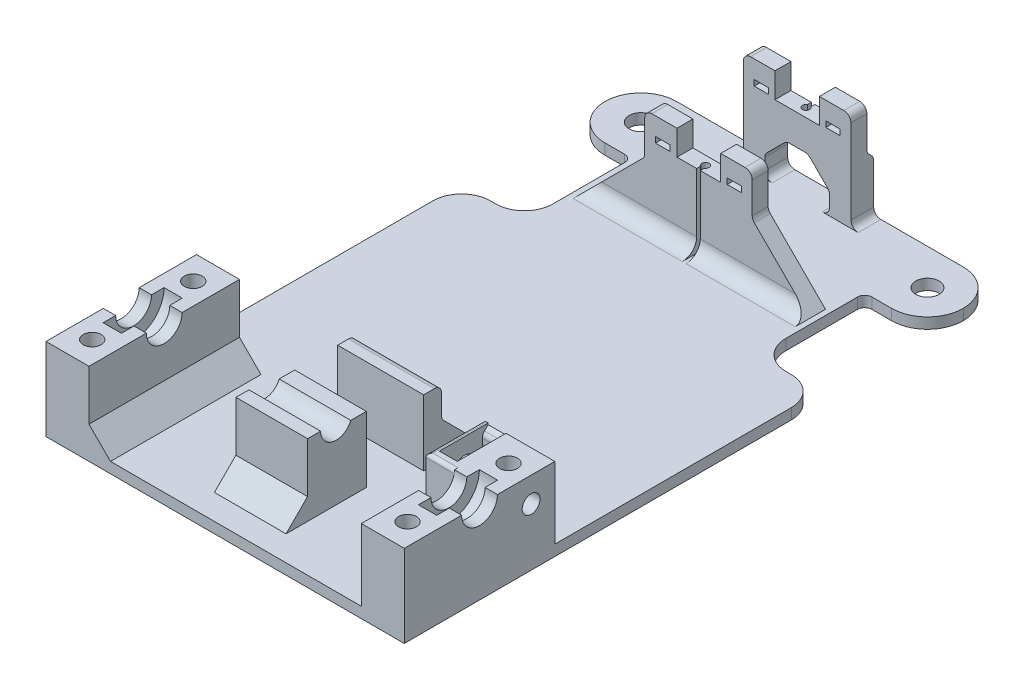
SolidWorks part; units mm, degrees
ref_plane "Front Plane" through (0, 0, 0) normal (0, 0, 1) x (1, 0, 0)
ref_plane "Top Plane" through (0, 0, 0) normal (0, 1, 0) x (1, 0, 0)
ref_plane "Right Plane" through (0, 0, 0) normal (1, 0, 0) x (0, 0, -1)
sketch "Sketch1" plane through (0, 0, 0) normal (0, 1, 0) x (1, 0, 0)
  line L0 (8, 116) -> (9.5, 116)
  line L1 (0, 0) -> (100, 0)
  line L2 (0, 0) -> (0, 108)
  line L5 (17.5, 124) -> (17.5, 146)
  line L7 (50, 0) -> (50, 146) construction
  line L8 (17.5, 146) -> (82.5, 146)
  line L9 (82.5, 124) -> (82.5, 146)
  line L10 (100, 0) -> (100, 108)
  line L11 (92, 116) -> (90.5, 116)
  arc A2 (9.5, 116) -> (17.5, 124) centre (9.5, 124) ccw
  arc A3 (8, 116) -> (0, 108) centre (8, 108) ccw
  arc A4 (92, 116) -> (100, 108) centre (92, 108) cw
  arc A5 (90.5, 116) -> (82.5, 124) centre (90.5, 124) cw
  dimension "D4" = 8
  dimension "D1" = 50
  dimension "D5" = 17.5
  dimension "D6" = 30
  dimension "D7" = 108
extrude "Boss-Extrude1" add sketch "Sketch1" along normal blind 3 contours L10 A4 L11 A5 L9 L8 L5 A2 L0 A3 L2 L1
ref_plane "Mid Plane" through (50, 0, 0) normal (-1, 0, 0) x (0, 0, 1)
sketch "Sketch2" plane through (0, 3, 0) normal (0, 1, 0) x (1, 0, 0)
  line L1 (0, 0) -> (12, 0)
  line L2 (0, 0) -> (0, 42)
  line L3 (0, 42) -> (12, 42)
  line L4 (12, 0) -> (12, 42)
  line L5 (100, 0) -> (88, 0)
  line L6 (100, 0) -> (100, 42)
  line L7 (100, 42) -> (88, 42)
  line L8 (88, 0) -> (88, 42)
  dimension "D1" = 42
  dimension "D2" = 12
extrude "Boss-Extrude2" add sketch "Sketch2" along normal blind 20
ref_plane "Plane1" through (6, 0, 0) normal (1, 0, 0) x (0, 0, -1)
sketch "Sketch3" plane through (6, 0, 0) normal (1, 0, 0) x (0, 0, -1)
  line L1 (0, 23) -> (42, 23) construction
  circle A0 centre (21, 23) radius 8.5
  point P6 (21, 23)
  dimension "D1" = 17
extrude "Cut-Extrude1" cut sketch "Sketch3" against normal mid plane 5.1
sketch "Sketch4" plane through (0, 0, 0) normal (-1, 0, 0) x (0, 0, 1)
  line L0 (-42, 23) -> (0, 23) construction
  circle A0 centre (-21, 23) radius 5
  dimension "D1" = 10
extrude "Cut-Extrude2" cut sketch "Sketch4" against normal up to surface (12 mm away) contours A0 up to face at (12, 13, -21)
mirror "Mirror7" about plane through (50, 0, 0) normal (-1, 0, 0) of "Cut-Extrude2", "Cut-Extrude1"
sketch "Sketch5" plane through (0, 3, 0) normal (0, 1, 0) x (1, 0, 0)
  line L0 (91.45, 21) -> (12, 21) construction
  line L1 (91.45, 12.5) -> (91.45, 29.5) construction
  line L2 (12, 16) -> (12, 26) construction
sketch "Sketch6" plane through (50, 0, 0) normal (1, 0, 0) x (0, 0, -1)
  line L0 (16.6344, 23) -> (13, 23)
  line L1 (29, 3) -> (13, 3)
  line L3 (26, 23) -> (25.3656, 23)
  line L4 (13, 3) -> (13, 23)
  line L5 (42, 3) -> (108, 3) construction
  line L6 (21, 3) -> (21, 18) construction
  line L7 (26, 23) -> (42, 23) construction
  line L8 (26, 23) -> (26, 3)
  line L9 (25.0619, 21.4) -> (26, 21.4)
  line L10 (26, 21.4) -> (29.4, 21.4)
  line L11 (29.4, 21.4) -> (29.4, 3)
  line L12 (29, 3) -> (29.4, 3)
  arc A0 (16, 23) -> (26, 23) centre (21, 23) ccw construction
  arc A2 (16.6344, 23) -> (25.3656, 23) centre (21, 23) ccw
  point P6 (21, 18.6344)
  dimension "D1" = 8.7312
  dimension "D2" = 16
  dimension "D3" = 1.6
  dimension "D4" = 3.4
extrude "Boss-Extrude3" add sketch "Sketch6" along normal mid plane 20 contours L0 A2 L3 L8 L1 L4 | L12 L1 L8 L10 L11 region at (50, 11.8875, -19.2724) region at (50, 12.2, -27.7)
chamfer "Chamfer1" distance 6 angle 45 2 edges at (12, 3, -21) (50, 3, -13)
chamfer "Chamfer2" [suppressed] distance 14 angle 45
sketch "Sketch7" plane through (0, 23, 0) normal (0, 1, 0) x (1, 0, 0)
  line L0 (6, 12.5) -> (6, 6.9) construction
  line L1 (8.55, 12.5) -> (3.45, 12.5) construction
  line L2 (6, 29.5) -> (6, 35.1) construction
  line L3 (3.45, 29.5) -> (8.55, 29.5) construction
  line L4 (50, 0) -> (50, 39.4651) construction
  line L5 (60, 0) -> (40, 0) construction
  line L6 (94, 29.5) -> (94, 35.1) construction
  line L7 (94, 12.5) -> (94, 6.9) construction
  circle A2 centre (6, 35.1) radius 2.5
  circle A3 centre (6, 6.9) radius 2.5
  circle A4 centre (94, 6.9) radius 2.5
  circle A5 centre (94, 35.1) radius 2.5
  dimension "D1" = 5
  dimension "D2" = 5.6
extrude "Cut-Extrude3" cut sketch "Sketch7" against normal up to next
sketch "Sketch8" plane through (0, 3, 0) normal (0, 1, 0) x (1, 0, 0)
  line L0 (36, 27) -> (36, 47) construction
  line L1 (18, 0) -> (88, 0) construction
  line L2 (30, 27) -> (30, 47) construction
  line L3 (0, 42) -> (0, 108) construction
  line L5 (30, 47) -> (36, 47) construction
  line L6 (36, 27) -> (30, 27) construction
  line L11 (29, 46.2) -> (37, 46.2)
  line L12 (29, 46.2) -> (29, 47.8)
  line L17 (29, 27.8) -> (37, 27.8)
  line L18 (29, 27.8) -> (29, 26.2)
  line L19 (29, 26.2) -> (37, 26.2)
  line L20 (37, 27.8) -> (37, 26.2)
  line L21 (29, 27.8) -> (37, 26.2) construction
  line L22 (29, 26.2) -> (37, 27.8) construction
  line L23 (29, 47.8) -> (37, 47.8)
  line L24 (37, 46.2) -> (37, 47.8)
  line L25 (29, 46.2) -> (37, 47.8) construction
  line L26 (29, 47.8) -> (37, 46.2) construction
  point P1 (33, 47)
  point P3 (33, 27)
  point P8 (33, 27)
  point P11 (33, 47)
  dimension "D5" = 6
  dimension "D2" = 20
  dimension "D3" = 27
  dimension "D4" = 36
  dimension "D7" = 8
  dimension "D8" = 1.6
extrude "Cut-Extrude4" cut sketch "Sketch8" against normal up to next
fillet "Fillet1" [suppressed] radius 2.54
sketch "Sketch9" plane through (0, 3, 0) normal (0, 1, 0) x (1, 0, 0)
  line L5 (80, 26) -> (88, 26)
  line L10 (49, 35.4) -> (80, 35.4) construction
  line L11 (49, 33.45) -> (49, 37.35) construction
  line L13 (80, 42) -> (88, 42)
  line L14 (80, 42) -> (80, 26)
  line L16 (88, 42) -> (88, 26)
  line L19 (88, 42) -> (88, 26) construction
  line L20 (100, 42) -> (88, 42) construction
  dimension "D2" = 8
extrude "Boss-Extrude4" add sketch "Sketch9" along normal up to surface (20 mm away) up to face at (94, 23, -37.6)
sketch "Sketch11" plane through (80, 0, 0) normal (-1, 0, 0) x (0, 0, 1)
  circle A0 centre (-35.4, 16) radius 5.55
  arc A2 (-36.4409, 14.92) -> (-36.3577, 17.1545) centre (-35.4, 16) ccw construction
  dimension "D3" = 11.1
extrude "Cut-Extrude6" cut sketch "Sketch11" against normal blind 5 from offset 1.4 offset against normal yes
sketch "Sketch12" plane through (80, 0, 0) normal (-1, 0, 0) x (0, 0, 1)
  line L0 (-40.4, 18.4088) -> (-40.4, 23)
  line L1 (-42, 23) -> (-26, 23) construction
  line L2 (-40.4, 23) -> (-30.4, 23)
  line L3 (-30.4, 23) -> (-30.4, 18.4088)
  line L4 (-35.4, 16) -> (-35.4, 23) construction
  circle A0 centre (-35.4, 16) radius 5.55 construction
  arc A1 (-30.4, 18.4088) -> (-40.4, 18.4088) centre (-35.4, 16) ccw
  dimension "D1" = 10
extrude "Cut-Extrude7" cut sketch "Sketch12" against normal blind 5 from offset 1.4 offset against normal yes
chamfer "Chamfer3" distance 2 angle 45 2 edges at (83.9, 23, -40.4) (83.9, 23, -30.4)
sketch "Sketch13" plane through (80, 0, 0) normal (-1, 0, 0) x (0, 0, 1)
  circle A0 centre (-35.4, 16) radius 2.5
  dimension "D1" = 5
extrude "Cut-Extrude8" cut sketch "Sketch13" against normal up to surface (20 mm away) up to face at (100, 11.625, -42.75)
fillet "Fillet3" radius 2 2 edges at (83.9, 21, -40.4) (83.9, 21, -30.4)
fillet "Fillet5" radius 1 2 edges at (84, 23, -26) (80, 23, -34) tangent propagation no
sketch "Sketch14" plane through (0, 3, 0) normal (0, 1, 0) x (1, 0, 0)
  line L1 (40, 41.4) -> (64, 41.4)
  line L2 (40, 41.4) -> (40, 46.4)
  line L3 (40, 46.4) -> (64, 46.4)
  line L4 (64, 41.4) -> (64, 46.4)
  line L5 (40, 25.0619) -> (40, 29.4) construction
  line L6 (60, 29.4) -> (40, 29.4) construction
  dimension "D1" = 24
  dimension "D2" = 5
  dimension "D3" = 12
extrude "Boss-Extrude5" add sketch "Sketch14" along normal up to surface (18.4 mm away) up to face at (50, 21.4, -27.2309)
chamfer "Chamfer4" distance 10 angle 45 1 edges at (52, 3, -46.4)
sketch "Sketch15" plane through (0, 3, 0) normal (0, 1, 0) x (1, 0, 0)
  line L0 (17.5, 146) -> (82.5, 146) construction
  line L1 (0, 146) -> (100, 146)
  line L2 (0, 146) -> (0, 166)
  line L3 (0, 166) -> (100, 166)
  line L4 (100, 146) -> (100, 166)
  line L5 (100, 42) -> (100, 108) construction
  line L6 (0, 156) -> (100, 156) construction
  line L7 (50, 166) -> (50, 156) construction
  circle A0 centre (90, 156) radius 3.25
  circle A1 centre (10, 156) radius 3.25
  point P6 (50, 146)
  point P7 (50, 146)
  point P19 (50, 161)
  dimension "D2" = 6.5
  dimension "D3" = 40
  dimension "D1" = 20
extrude "Boss-Extrude6" add sketch "Sketch15" against normal up to surface (3 mm away) up to face at (33, 0, -47)
sketch "Sketch16" plane through (0, 3, 0) normal (0, 1, 0) x (1, 0, 0)
  line L0 (100, 166) -> (0, 166) construction
  line L1 (35, 164.1) -> (49.5, 164.1)
  line L2 (35, 164.1) -> (35, 159.65)
  line L3 (35, 159.65) -> (65, 159.65)
  line L4 (65, 164.1) -> (65, 159.65)
  line L5 (49.5, 164.1) -> (49.5, 162.966)
  line L6 (50.5, 164.1) -> (50.5, 162.966)
  line L8 (50.5, 164.1) -> (65, 164.1)
  line L16 (49.5, 132.1) -> (49.5, 133.234)
  line L17 (35, 136.55) -> (65, 136.55)
  line L18 (35, 136.55) -> (35, 132.1)
  line L19 (35, 132.1) -> (49.5, 132.1)
  line L20 (65, 136.55) -> (65, 132.1)
  line L21 (50.5, 132.1) -> (50.5, 133.234)
  line L22 (50.5, 132.1) -> (65, 132.1)
  arc A0 (49.5, 162.966) -> (50.5, 162.966) centre (50, 162.1) ccw
  arc A2 (49.5, 133.234) -> (50.5, 133.234) centre (50, 134.1) cw
  point P6 (50, 166)
  point P7 (50, 136.55)
  point P13 (50, 159.65)
  dimension "D3" = 2
  dimension "D4" = 2
  dimension "D7" = 1
  dimension "D8" = 1
  dimension "D1" = 30
  dimension "D2" = 4.45
  dimension "D5" = 1
  dimension "D6" = 29.45
  dimension "D9" = 2
  dimension "D10" = 30
  dimension "D11" = 1.9
extrude "Boss-Extrude7" add sketch "Sketch16" along normal blind 20.5 contours L4 L3 L2 L1 L5 A0 L6 L8 | L18 L19 L16 A2 L21 L22 L20 L17
sketch "Sketch17" plane through (0, 0, -166) normal (0, 0, -1) x (-1, 0, 0)
  line L0 (-91.45, 3) -> (-12, 3) construction
  line L1 (-59, 3) -> (-41, 3)
  line L2 (-59, 3) -> (-59, 15)
  line L3 (-59, 15) -> (-41, 15)
  line L4 (-41, 3) -> (-41, 15)
  line L6 (-100, 0) -> (0, 0) construction
  point P13 (-50, 0)
  point P14 (-50, 3)
  dimension "D1" = 12
  dimension "D2" = 18
extrude "Cut-Extrude9" cut sketch "Sketch17" against normal up to surface (6.35 mm away) up to face at (50, 13.25, -159.65)
fillet "Fillet7" radius 10 4 edges at (0, 1.5, -146) (0, 1.5, -166) (100, 1.5, -166) (100, 1.5, -146)
chamfer "Chamfer5" distance 16 angle 45 4 edges at (35, 3, -134.325) (62, 3, -164.1) (38, 3, -164.1) (65, 3, -134.325)
chamfer "Chamfer6" distance 6 angle 45 2 edges at (41, 15, -162.825) (59, 15, -162.825)
fillet "Fillet6" radius 2 18 edges at (52, 13, -46.4) (52, 21.4, -46.4) (17.5, 1.5, -146) (82.5, 1.5, -146) (42.25, 19, -164.1) (57.75, 19, -164.1) (57.75, 17.1, -166) (42.25, 17.1, -166) (41, 9, -162.825) (47, 15, -162.825) (53, 15, -162.825) (59, 9, -162.825) (35, 3, -162.825) (65, 3, -162.825) (59, 3, -162.825) (41, 3, -162.825) (35, 19, -134.325) (65, 19, -134.325)
sketch "Sketch18" plane through (0, 23.5, 0) normal (0, 1, 0) x (1, 0, 0)
  line L1 (44.1, 136.55) -> (56.1, 136.55) construction
  line L2 (44.1, 136.55) -> (44.1, 132.1) construction
  line L3 (44.1, 132.1) -> (56.1, 132.1) construction
  line L4 (56.1, 136.55) -> (56.1, 132.1) construction
  line L5 (44.1, 136.55) -> (56.1, 132.1) construction
  line L6 (44.1, 132.1) -> (56.1, 136.55) construction
  line L7 (19, 132.1) -> (49.5, 132.1) construction
  line L8 (56.2, 132.1) -> (65, 132.1)
  line L9 (56.2, 132.1) -> (56.2, 136.55)
  line L10 (56.2, 136.55) -> (65, 136.55)
  line L11 (65, 132.1) -> (65, 136.55)
  line L12 (44, 132.1) -> (35, 132.1)
  line L13 (44, 132.1) -> (44, 136.55)
  line L14 (44, 136.55) -> (35, 136.55)
  line L15 (35, 132.1) -> (35, 136.55)
  line L16 (35, 136.55) -> (35, 132.1) construction
  line L17 (35, 136.55) -> (35, 132.1) construction
  line L18 (56.1, 134.325) -> (56.2, 134.325) construction
  line L19 (44, 134.325) -> (44.1, 134.325) construction
  line L20 (57, 159.65) -> (67, 159.65) construction
  line L21 (65, 159.65) -> (56.2, 159.65)
  line L22 (65, 159.65) -> (65, 164.1)
  line L23 (65, 164.1) -> (56.2, 164.1)
  line L24 (56.2, 159.65) -> (56.2, 164.1)
  line L25 (65, 164.1) -> (65, 159.65) construction
  line L27 (35, 164.1) -> (49.5, 164.1) construction
  line L28 (35, 159.65) -> (43.8, 159.65)
  line L29 (35, 159.65) -> (35, 164.1)
  line L30 (35, 164.1) -> (43.8, 164.1)
  line L31 (43.8, 159.65) -> (43.8, 164.1)
  line L32 (19, 136.55) -> (81, 136.55) construction
  point P0 (50.1, 134.325)
  dimension "D1" = 12
  dimension "D2" = 0.1
  dimension "D3" = 8.8
extrude "Boss-Extrude8" add sketch "Sketch18" along normal blind 7
fillet "Fillet9" radius 4 2 edges at (34.25, 3, -132.1) (65.75, 3, -132.1)
fillet "Fillet8" radius 2 4 edges at (35, 30.5, -134.325) (65, 30.5, -134.325) (35, 30.5, -161.875) (65, 30.5, -161.875)
sketch "Sketch19" plane through (0, 0, -164.1) normal (0, 0, -1) x (-1, 0, 0)
  line L0 (-40, 30.5) -> (-40, 25.5) construction
  line L3 (-62, 23.9) -> (-58, 23.9)
  line L4 (-62, 23.9) -> (-62, 25.5)
  line L5 (-62, 25.5) -> (-58, 25.5)
  line L6 (-58, 23.9) -> (-58, 25.5)
  line L9 (-42, 23.9) -> (-38, 23.9)
  line L10 (-42, 23.9) -> (-42, 25.5)
  line L11 (-42, 25.5) -> (-38, 25.5)
  line L12 (-38, 23.9) -> (-38, 25.5)
  line L14 (-60, 30.5) -> (-60, 25.5) construction
  line L16 (-35, 28.5) -> (-35, 19.8284) construction
  line L17 (-65, 28.5) -> (-65, 19.8284) construction
  line L18 (-43.8, 30.5) -> (-37, 30.5) construction
  dimension "D1" = 1.6
  dimension "D2" = 4
  dimension "D3" = 5
  dimension "D4" = 5
  dimension "D5" = 5
extrude "Cut-Extrude10" cut sketch "Sketch19" against normal up to surface (32 mm away) up to face at (39.0156, 21.011, -132.1)
